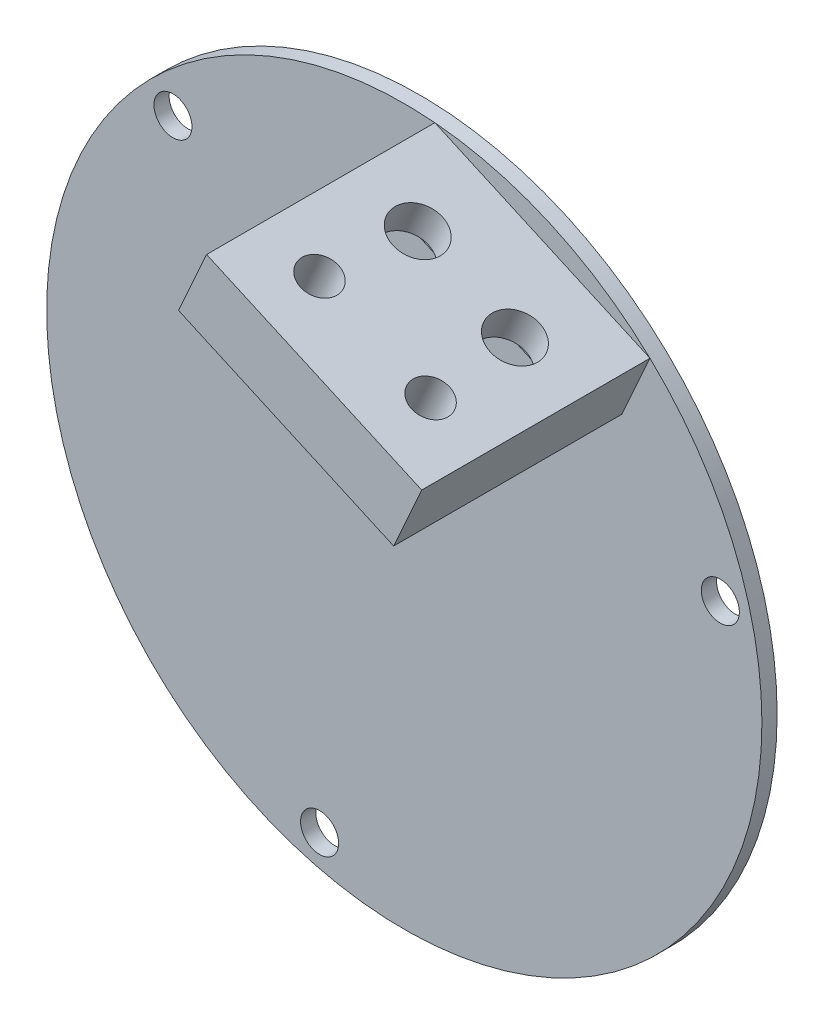
SolidWorks part; units mm, degrees
ref_plane "Plan de face" through (0, 0, 0) normal (0, 0, 1) x (1, 0, 0)
ref_plane "Plan de dessus" through (0, 0, 0) normal (0, 1, 0) x (1, 0, 0)
ref_plane "Plan de droite" through (0, 0, 0) normal (1, 0, 0) x (0, 0, -1)
sketch "Sketch1" plane through (0, 0, 0) normal (0, 0, 1) x (1, 0, 0)
  circle A0 centre (0, 0) radius 47
  dimension "D1" = 94
extrude "Boss-Extrude1" add sketch "Sketch1" along normal blind 2
sketch "Sketch3" plane through (0, 0, 0) normal (0, 0, -1) x (-1, 0, 0)
  line L0 (0, 0) -> (0, 43) construction
  line L1 (0, 0) -> (30.4056, 30.4056) construction
  circle A0 centre (0, 0) radius 43 construction
  circle A1 centre (30.4056, 30.4056) radius 2.5
  circle A2 centre (11.1292, -41.5348) radius 2.5
  circle A3 centre (-41.5348, 11.1292) radius 2.5
  point P13 (0, 0)
  dimension "D1" = 86
  dimension "D2" = 5
  dimension "D3" = 45
  dimension "D4" = 3
extrude "Cut-Extrude1" cut sketch "Sketch3" against normal through all contours A3 | A1 | A2
sketch "Sketch4" plane through (0, 0, 2) normal (0, 0, 1) x (1, 0, 0)
  line L0 (-22.2135, -49.5439) -> (25.9538, 57.8861) construction
  line L3 (-30.4056, 30.4056) -> (42.9287, -2.4745) construction
  line L6 (4.021, 46.8277) -> (32.2879, 34.1539)
  line L7 (32.2879, 34.1539) -> (28.6058, 25.9416)
  line L8 (28.6058, 25.9416) -> (0.3389, 38.6154)
  line L9 (0.3389, 38.6154) -> (4.021, 46.8277)
  circle A2 centre (-30.4056, 30.4056) radius 2.5 construction
  circle A3 centre (0, 0) radius 47 construction
  circle A6 centre (-30.4056, 30.4056) radius 2.5 construction
  circle A7 centre (0, 0) radius 47 construction
  circle A8 centre (-30.4056, 30.4056) radius 4.25 construction
  circle A9 centre (42.9287, -2.4745) radius 2.5 construction
  circle A10 centre (42.9287, -2.4745) radius 4.25 construction
  circle A11 centre (-22.2135, -49.5439) radius 2.5 construction
  circle A12 centre (-22.2135, -49.5439) radius 4.25 construction
  point P16 (-3.2301, -7.2043)
  point P18 (14.444, 32.2151)
  point P19 (18.1544, 40.4908)
  dimension "D1" = 8.5
  dimension "D3" = 9
  dimension "D2" = 3
extrude "Boss-Extrude2" add sketch "Sketch4" along normal blind 30
sketch "Sketch8" plane through (18.1544, 40.4908, 0) normal (0.4091, 0.9125, 0) x (0.9125, -0.4091, 0)
  line L0 (0, -2) -> (0, -32) construction
  line L3 (15.489, -2) -> (-15.489, -2) construction
  line L4 (15.489, -32) -> (-15.489, -32) construction
  line L5 (-7, -12) -> (7, -12) construction
  line L6 (0, -24) -> (8, -24) construction
  circle A0 centre (7, -12) radius 3.25
  circle A3 centre (-7, -12) radius 3.25
  circle A4 centre (8, -24) radius 2.5
  circle A5 centre (-8, -24) radius 2.5
  point P9 (0, -12)
  point P12 (0, -24)
  point P16 (6, -24)
  dimension "D3" = 6.5
  dimension "D4" = 5
  dimension "D1" = 7
  dimension "D2" = 8
  dimension "D6" = 12
  dimension "D7" = 10
extrude "Cut-Extrude3" cut sketch "Sketch8" against normal up to next
ref_plane "Plane1" through (16.3134, 36.3847, 0) normal (0.4091, 0.9125, 0) x (0.9125, -0.4091, 0)
ref_plane "Plane2" through (14.8815, 33.191, 0) normal (0.4091, 0.9125, 0) x (0.9125, -0.4091, 0)
sketch "Sketch9" plane through (14.4724, 32.2785, 0) normal (-0.4091, -0.9125, 0) x (0.9125, -0.4091, 0)
  line L0 (0, 2) -> (0, 32) construction
  line L1 (47, 2) -> (-47, 2) construction
  line L2 (-15.489, 32) -> (15.489, 32) construction
  line L3 (-1.5, 18.5) -> (-12.5, 18.5)
  line L4 (1.5, 5.5) -> (12.5, 5.5)
  line L5 (1.5, 5.5) -> (1.5, 18.5)
  line L6 (1.5, 18.5) -> (12.5, 18.5)
  line L7 (12.5, 5.5) -> (12.5, 18.5)
  line L8 (1.5, 5.5) -> (12.5, 18.5) construction
  line L9 (1.5, 18.5) -> (12.5, 5.5) construction
  line L10 (-12.5, 5.5) -> (-12.5, 18.5)
  line L11 (-1.5, 5.5) -> (-12.5, 5.5)
  line L12 (-1.5, 5.5) -> (-1.5, 18.5)
  circle A1 centre (7, 12) radius 3.25 construction
  circle A3 centre (7, 12) radius 3.25 construction
  dimension "D1" = 13
  dimension "D2" = 11
extrude "Cut-Extrude4" cut sketch "Sketch9" against normal up to surface (4.5 mm away) up to plane "Plane1"
sketch "Sketch10" plane through (14.4724, 32.2785, 0) normal (-0.4091, -0.9125, 0) x (0.9125, -0.4091, 0)
  line L0 (0, 2) -> (0, 32) construction
  line L1 (-15.489, 2) -> (15.489, 2) construction
  line L2 (-15.489, 32) -> (15.489, 32) construction
  line L3 (-8, 24) -> (8, 24) construction
  line L4 (5.25, 25.8767) -> (5.25, 22.1233) construction
  line L5 (5.25, 25.199) -> (5.25, 22.801)
  line L6 (-5.25, 25.199) -> (-5.25, 22.801)
  circle A1 centre (8, 24) radius 2.5 construction
  circle A4 centre (8, 24) radius 2.5 construction
  arc A6 (5.25, 25.199) -> (5.25, 22.801) centre (8, 24) cw
  arc A7 (-5.25, 25.199) -> (-5.25, 22.801) centre (-8, 24) ccw
  point P12 (0, 24)
  point P14 (5.25, 24)
  dimension "D1" = 2.75
  dimension "D2" = 3
extrude "Cut-Extrude5" cut sketch "Sketch10" against normal up to surface (1 mm away) up to plane "Plane2"
